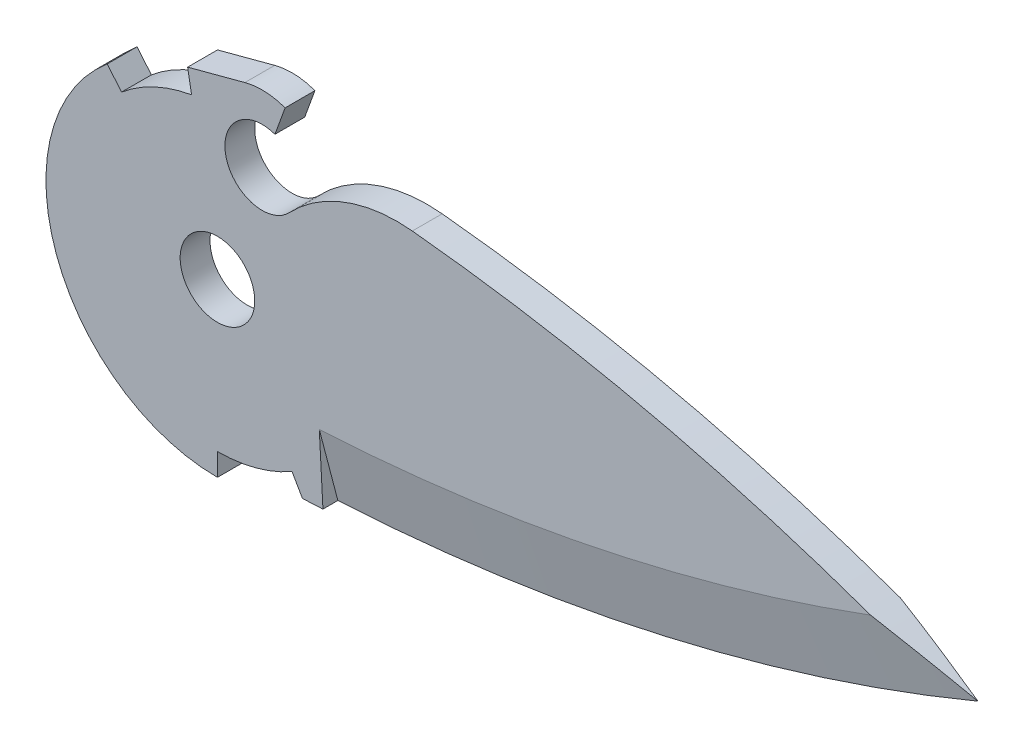
SolidWorks part; units mm, degrees
material "Obyčejná uhlíková ocel"
ref_plane "Přední rovina" through (0, 0, 0) normal (0, 0, 1) x (1, 0, 0)
ref_plane "Horní rovina" through (0, 0, 0) normal (0, 1, 0) x (1, 0, 0)
ref_plane "Pravá rovina" through (0, 0, 0) normal (1, 0, 0) x (0, 0, -1)
sketch "Skica1" plane through (0, 0, 0) normal (0, 0, 1) x (1, 0, 0)
  line L0 (0, 0) -> (28.9614, 0) construction
  line L1 (1.8411, 12.3482) -> (-1.997, 11.3253)
  line L2 (-1.997, 11.3253) -> (-1.7365, 9.8481)
  line L3 (0, 10) -> (0, -10) construction
  line L4 (3, 8) -> (3, 16.5233) construction
  line L5 (3.8551, 10.3492) -> (4.5391, 12.2286)
  line L6 (-7.3921, 8.8095) -> (-6.4279, 7.6604)
  line L7 (0, 0) -> (58.3677, 0) construction
  line L8 (5, -8.6603) -> (5.7013, -9.8749)
  line L9 (0, -10) -> (0, -11.5)
  circle A0 centre (0, 0) radius 2.5
  arc A1 (-1.7365, 9.8481) -> (-6.4279, 7.6604) centre (0, 0) ccw
  arc A2 (13.0692, 9.3414) -> (50, 0) centre (0, -120) cw
  arc A3 (5.7013, -9.8749) -> (50, 0) centre (0, 120) ccw
  arc A4 (3.8551, 10.3492) -> (4.8128, 6.2784) centre (3, 8) ccw
  arc A5 (13.0692, 9.3414) -> (4.8128, 6.2784) centre (12.0638, -0.6079) ccw
  arc A6 (4.5391, 12.2286) -> (1.8411, 12.3482) centre (3, 8) ccw
  arc A7 (0, -11.5) -> (-7.3921, 8.8095) centre (0, 0) cw
  arc A8 (0, -10) -> (5, -8.6603) centre (0, 0) ccw
  dimension "D1" = 10
  dimension "D2" = 5
  dimension "D3" = 50
  dimension "D5" = 2.5
  dimension "D6" = 2
  dimension "D8" = 10
  dimension "D11" = 10
  dimension "D12" = 0
  dimension "D13" = 30
  dimension "D14" = 130
  dimension "D15" = 30
  dimension "D4" = 3
  dimension "D7" = 20
  dimension "D9" = 1.5
  dimension "D10" = 8
extrude "Přidat vysunutím1" add sketch "Skica1" along normal mid plane 2
ref_plane "Rovina1" through (50, 0, 1) normal (0.9231, 0.3846, 0) x (0, 0, -1)
sketch "Skica6" plane through (50, 0, 1) normal (0.9231, 0.3846, 0) x (0, 0, -1)
  line L0 (1, 0) -> (2, 4.5107)
  line L1 (0, 0) -> (2, 0) construction
  line L2 (2, 0) -> (2, 22.827) construction
  line L3 (1, 0) -> (0, 4.5107) construction
  line L4 (0, 22.827) -> (0, 0) construction
  line L5 (1, 0) -> (2, 0)
  line L6 (2, 0) -> (2, 4.5107)
  dimension "D1" = 25
revolve "Odebrat rotací2" cut sketch "Skica6" angle 19.5 about axis through (0, 120, 1) along (0, 0, -1)
mirror "Zrcadlit1" about plane through (0, 0, 0) normal (0, 0, 1) of "Odebrat rotací2"
sketch "Skica5" plane through (0, 0, -1) normal (0, 0, -1) x (-1, 0, 0)
  circle A0 centre (-13.6099, 7.7362) radius 0.9715
extrude "Přidat vysunutím2" [suppressed] add sketch "Skica5" along normal blind 2
